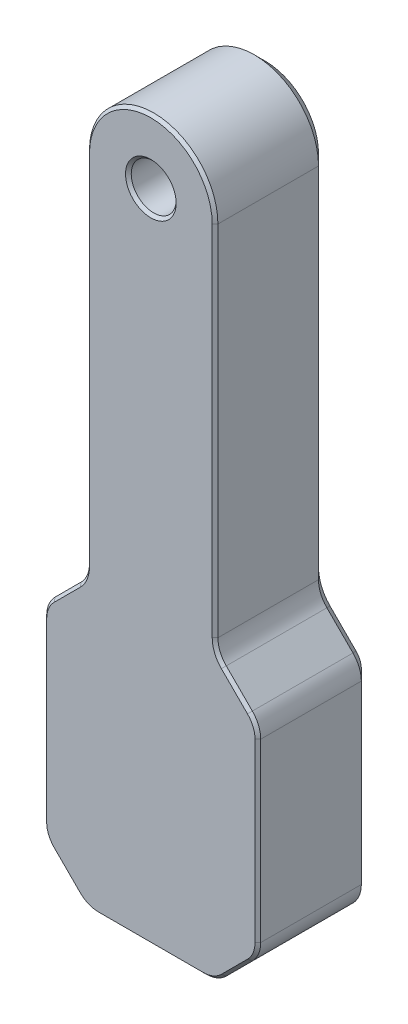
SolidWorks part; units mm, degrees
ref_plane "Front" through (0, 0, 0) normal (0, 0, 1) x (1, 0, 0)
ref_plane "Top" through (0, 0, 0) normal (0, 1, 0) x (1, 0, 0)
ref_plane "Right" through (0, 0, 0) normal (1, 0, 0) x (0, 0, -1)
sketch "Sketch1" plane through (0, 0, 0) normal (0, 0, 1) x (1, 0, 0)
  line L4 (0, 0) -> (0, -45.9352) construction
  line L5 (-149.5, -65.9352) -> (0, -65.9352) construction
  line L6 (0, -65.9352) -> (0, -45.9352) construction
  line L13 (-4.5, 0) -> (-4.5, -25.9352)
  line L20 (-4.5, -25.9352) -> (-7.5, -28.9352)
  line L27 (-7.5, -28.9352) -> (-7.5, -42.9352)
  line L28 (-7.5, -42.9352) -> (-4.5, -45.9352)
  line L29 (-4.5, -45.9352) -> (4.5, -45.9352)
  line L30 (4.5, -45.9352) -> (7.5, -42.9352)
  line L31 (7.5, -42.9352) -> (7.5, -28.9352)
  line L32 (7.5, -28.9352) -> (4.5, -25.9352)
  line L33 (4.5, -25.9352) -> (4.5, 0)
  arc A2 (-4.5, 0) -> (4.5, 0) centre (0, 0) cw
  dimension "D1" = 4.5
  dimension "D2" = 45
  dimension "D3" = 20
  dimension "D4" = 45
  dimension "D5" = 15
  dimension "D6" = 3
  dimension "D7" = 14
extrude "Boss-Extrude2" add sketch "Sketch1" along normal blind 8
sketch "Sketch5" plane through (0, 0, 8) normal (0, 0, 1) x (1, 0, 0)
  line L17 (-3.25, 0) -> (-3.25, -26.4529)
  line L18 (-3.25, 0) -> (-3.25, -26.4529)
  line L28 (3.25, -26.4529) -> (3.25, 0)
  line L29 (3.25, -26.4529) -> (3.25, 0)
  line L51 (-3.25, -26.4529) -> (3.25, -26.4529)
  line L507 (-3.25, -26.4529) -> (-6.25, -29.4529)
  line L508 (-6.25, -29.4529) -> (-6.25, -42.4174)
  line L509 (-6.25, -42.4174) -> (-3.9822, -44.6852)
  line L510 (-3.9822, -44.6852) -> (3.9822, -44.6852)
  line L511 (3.9822, -44.6852) -> (6.25, -42.4174)
  line L512 (6.25, -42.4174) -> (6.25, -29.4529)
  line L513 (6.25, -29.4529) -> (3.25, -26.4529)
  line L516 (-3.25, -26.4529) -> (-6.25, -29.4529)
  line L517 (-6.25, -29.4529) -> (-6.25, -42.4174)
  line L518 (-6.25, -42.4174) -> (-3.9822, -44.6852)
  line L519 (-3.9822, -44.6852) -> (3.9822, -44.6852)
  line L520 (3.9822, -44.6852) -> (6.25, -42.4174)
  line L521 (6.25, -42.4174) -> (6.25, -29.4529)
  line L522 (6.25, -29.4529) -> (3.25, -26.4529)
  arc A3 (3.25, 0) -> (-3.25, 0) centre (0, 0) ccw
  arc A5 (3.25, 0) -> (-3.25, 0) centre (0, 0) ccw construction
  dimension "D1" = 1.25
extrude "Rod Pocket" cut sketch "Sketch5" against normal offset from surface (6 mm away) 2 rebuild error yes up to face at (0, -28.2981, 0)
fillet "Pocket Fillets" radius 1 rebuild error yes
sketch "Handle Profile Guide" plane through (0, 0, 0) normal (0, 0, 1) x (1, 0, 0)
  line L40 (-6.1, -3.882) -> (-6.1, -16.018)
  line L41 (-5.851, -16.6191) -> (-4.1691, -18.301)
  line L42 (-3.568, -18.55) -> (3.568, -18.55)
  line L43 (4.1691, -18.301) -> (5.851, -16.6191)
  line L44 (6.1, -16.018) -> (6.1, -3.882)
  line L45 (5.851, -3.2809) -> (3.4072, -0.8371)
  line L46 (2.8061, -0.5881) -> (-2.8061, -0.5881)
  line L47 (-3.4072, -0.8371) -> (-5.851, -3.2809)
  line L48 (-6.1, -3.882) -> (-6.1, -16.018)
  line L49 (-5.851, -16.6191) -> (-4.1691, -18.301)
  line L50 (-3.568, -18.55) -> (3.568, -18.55)
  line L51 (4.1691, -18.301) -> (5.851, -16.6191)
  line L52 (6.1, -16.018) -> (6.1, -3.882)
  line L53 (5.851, -3.2809) -> (3.4072, -0.8371)
  line L54 (2.8061, -0.5881) -> (-2.8061, -0.5881)
  line L55 (-3.4072, -0.8371) -> (-5.851, -3.2809)
  arc A40 (-5.851, -3.2809) -> (-6.1, -3.882) centre (-5.25, -3.882) ccw
  arc A41 (-6.1, -16.018) -> (-5.851, -16.6191) centre (-5.25, -16.018) ccw
  arc A42 (-4.1691, -18.301) -> (-3.568, -18.55) centre (-3.568, -17.7) ccw
  arc A43 (3.568, -18.55) -> (4.1691, -18.301) centre (3.568, -17.7) ccw
  arc A44 (5.851, -16.6191) -> (6.1, -16.018) centre (5.25, -16.018) ccw
  arc A45 (6.1, -3.882) -> (5.851, -3.2809) centre (5.25, -3.882) ccw
  arc A46 (3.4072, -0.8371) -> (2.8061, -0.5881) centre (2.8061, -1.4381) ccw
  arc A47 (-2.8061, -0.5881) -> (-3.4072, -0.8371) centre (-2.8061, -1.4381) ccw
  arc A48 (-5.851, -3.2809) -> (-6.1, -3.882) centre (-5.25, -3.882) ccw
  arc A49 (-6.1, -16.018) -> (-5.851, -16.6191) centre (-5.25, -16.018) ccw
  arc A50 (-4.1691, -18.301) -> (-3.568, -18.55) centre (-3.568, -17.7) ccw
  arc A51 (3.568, -18.55) -> (4.1691, -18.301) centre (3.568, -17.7) ccw
  arc A52 (5.851, -16.6191) -> (6.1, -16.018) centre (5.25, -16.018) ccw
  arc A53 (6.1, -3.882) -> (5.851, -3.2809) centre (5.25, -3.882) ccw
  arc A54 (3.4072, -0.8371) -> (2.8061, -0.5881) centre (2.8061, -1.4381) ccw
  arc A55 (-2.8061, -0.5881) -> (-3.4072, -0.8371) centre (-2.8061, -1.4381) ccw
  dimension "D1" = 0.15
ref_plane "Latch Plane" through (0, 0, 5) normal (0, 0, 1) x (1, 0, 0)
sketch "Sketch8" plane through (0, 0, 5) normal (0, 0, 1) x (1, 0, 0)
  line L0 (-7.35, -39.9352) -> (-7.35, -31.9352)
  line L1 (-5.85, -33.4352) -> (-5.85, -38.4352)
  line L2 (-6.25, -29.4529) -> (-6.25, -42.4174) construction
  line L3 (-6.25, -35.9352) -> (-5.85, -35.9352) construction
  arc A0 (-7.35, -31.9352) -> (-5.85, -33.4352) centre (-7.35, -33.4352) cw
  arc A1 (-5.85, -38.4352) -> (-7.35, -39.9352) centre (-7.35, -38.4352) cw
  dimension "D1" = 1.5
  dimension "D2" = 0.4
  dimension "D3" = 8
revolve "Latch  Bump" add sketch "Sketch8" angle 90 about L0 other way angle 90
fillet "Latch Bump Fillet" radius 2 rebuild error yes
mirror "Latch Bumps" about plane through (0, 0, 0) normal (1, 0, 0) rebuild error yes
fillet "Profile Fillets" radius 2 8 edges at (-4.5, -25.9352, 4) (-7.5, -28.9352, 4) (-7.5, -42.9352, 4) (-4.5, -45.9352, 4) (4.5, -45.9352, 4) (7.5, -42.9352, 4) (7.5, -28.9352, 4) (4.5, -25.9352, 4)
chamfer "Insert Cham" distance 0.5 angle 60 rebuild error yes
sketch "Sketch6" plane through (0, 0, 0) normal (0, 0, -1) x (-1, 0, 0)
  circle A0 centre (0, 0) radius 2.875
  dimension "D1" = 5.75
extrude "Countersink" cut sketch "Sketch6" against normal blind 2.6
sketch "Sketch7" plane through (0, 0, 0) normal (0, 0, 1) x (1, 0, 0)
  circle A0 centre (0, 0) radius 1.575
  dimension "D1" = 3.15
extrude "Through Hole" cut sketch "Sketch7" along normal through all
chamfer "Deburs" distance 0.2 angle 45 21 edges at (1.575, 0, 8) (-1.575, 0, 2.6) (-2.875, 0, 0) (0, 4.5, 8) (0, -45.9352, 8) (4.4369, -45.7829, 8) (-4.4369, -45.7829, 8) (6, -44.4352, 8) (-6, -44.4352, 8) (7.3478, -42.8721, 8) (-7.3478, -42.8721, 8) (7.5, -35.9352, 8) (-7.5, -35.9352, 8) (7.3478, -28.9982, 8) (-7.3478, -28.9982, 8) (6, -27.4352, 8) (-6, -27.4352, 8) (4.6522, -25.8721, 8) (-4.6522, -25.8721, 8) (4.5, -12.5534, 8) (-4.5, -12.5534, 8)
chamfer "Outside Chamfer" distance 0.75 angle 45 18 edges at (0, 4.5, 0) (-4.4369, -45.7829, 0) (0, -45.9352, 0) (4.4369, -45.7829, 0) (6, -44.4352, 0) (7.3478, -42.8721, 0) (7.5, -35.9352, 0) (7.3478, -28.9982, 0) (6, -27.4352, 0) (4.6522, -25.8721, 0) (4.5, -12.5534, 0) (-4.5, -12.5534, 0) (-4.6522, -25.8721, 0) (-6, -27.4352, 0) (-7.3478, -28.9982, 0) (-7.5, -35.9352, 0) (-7.3478, -42.8721, 0) (-6, -44.4352, 0)
ref_plane "Center of Handle" through (0, -9.5691, 0) normal (0, -1, 0) x (-1, 0, 0)
equation "\"D1@Sketch6\"=\"Hardware Head Countersink Diameter@Box Assy.Assembly\""
equation "\"D1@Sketch7\"=\"Hardware Clearance Hole Diameter@Box Assy.Assembly\""
equation "\"D1@Countersink\"=\"Nut Trap Depth@Box Assy.Assembly\""
